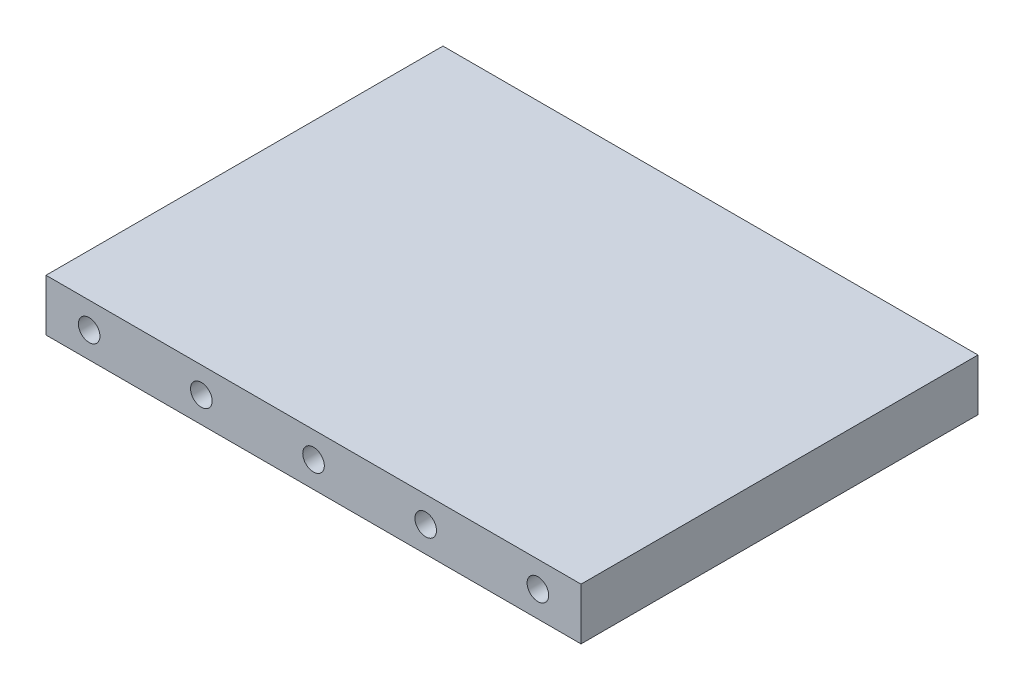
SolidWorks part; units mm, degrees
material "6061-T6 (SS)"
ref_plane "Front Plane" through (0, 0, 0) normal (0, 0, 1) x (1, 0, 0)
ref_plane "Top Plane" through (0, 0, 0) normal (0, 1, 0) x (1, 0, 0)
ref_plane "Right Plane" through (0, 0, 0) normal (1, 0, 0) x (0, 0, -1)
sketch "Sketch1" plane through (0, 0, 0) normal (0, 1, 0) x (1, 0, 0)
  line L1 (0, 0) -> (62, 0)
  line L2 (0, 0) -> (0, 46)
  line L3 (0, 46) -> (62, 46)
  line L4 (62, 0) -> (62, 46)
  dimension "D1" = 62
  dimension "D2" = 46
extrude "Boss-Extrude1" add sketch "Sketch1" along normal blind 6
sketch "Sketch5" plane through (0, 0, -46) normal (0, 0, -1) x (-1, 0, 0)
  line L1 (-62, 0) -> (0, 0) construction
  line L2 (-62, 6) -> (-62, 0) construction
  point P0 (-57, 3)
  point P12 (-44, 3)
  point P13 (-31, 3)
  point P14 (-18, 3)
  point P15 (-5, 3)
  dimension "D1" = 3
  dimension "D2" = 5
hole_wizard "Tap Drill for M3 Tap1" positions "Sketch5" profile "Sketch7" hole size "M3" standard "DIN" end condition through all
sketch "Sketch7" plane through (57, 3, -46) normal (1, 0, 0) x (0, 1, 0)
  line L0 (0, 0) -> (0, 46)
  line L1 (0, 46) -> (1.25, 46)
  line L2 (1.25, 46) -> (1.25, 0)
  line L5 (1.25, 0) -> (0, 0)
  line L11 (0, -6.35) -> (0, 107.95) construction
  dimension "Thru Hole Dia." = 2.5
  dimension "Thru Hole Depth" = 46
